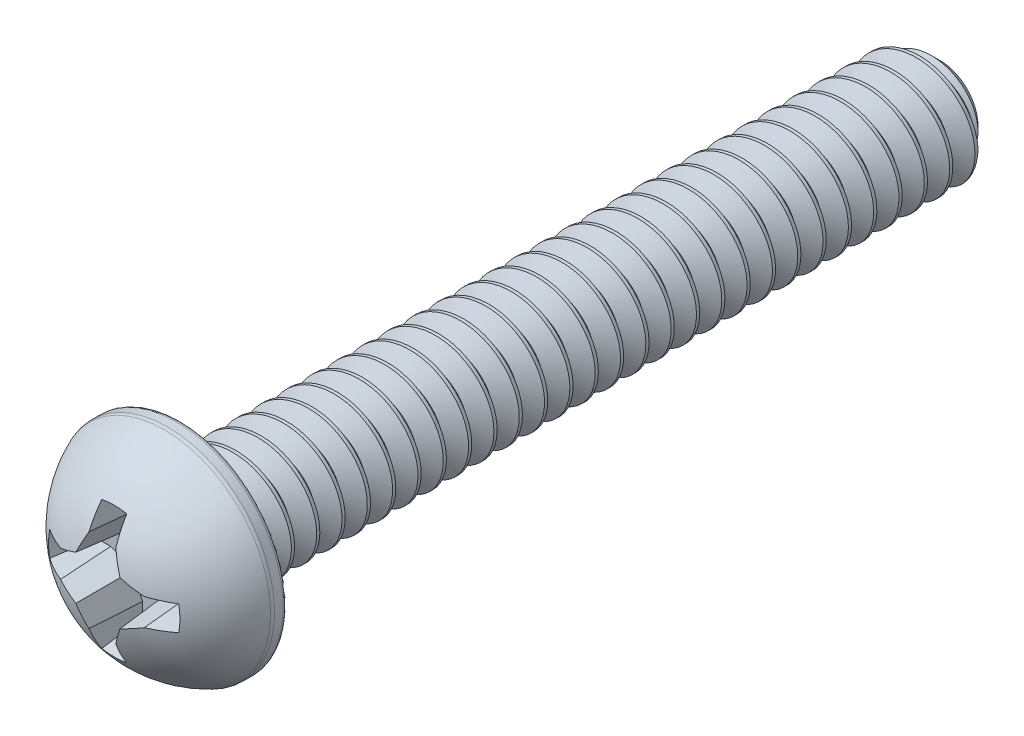
SolidWorks part; units mm, degrees
ref_plane "Front" through (0, 0, 0) normal (0, 0, 1) x (1, 0, 0)
ref_plane "Top" through (0, 0, 0) normal (0, 1, 0) x (1, 0, 0)
ref_plane "Right" through (0, 0, 0) normal (1, 0, 0) x (0, 0, -1)
sketch "Sketch1" plane through (0, 0, 0) normal (0, 0, 1) x (1, 0, 0)
  circle A0 centre (0, 0) radius 2.6797
  dimension "Head Dia" = 5.3594
extrude "Extrude3" add sketch "Sketch1" along normal blind 2.1844
sketch "Sketch11" plane through (0, 0, 0) normal (1, 0, 0) x (0, 0, -1)
  line L0 (0, 0) -> (-2.4384, 0) construction
  line L4 (-2.1844, 2.6797) -> (-2.1844, -2.6797) construction
  line L5 (-2.4384, 3.1064) -> (0, 3.1064)
  line L7 (0, 3.1064) -> (0, 2.5705)
  line L8 (-0.3277, 2.6797) -> (-0.1092, 2.6797)
  line L9 (0, -2.6797) -> (0, 2.6797) construction
  line L11 (0, 2.6797) -> (-2.1844, 2.6797) construction
  line L13 (-2.1844, 0) -> (-2.4384, 0)
  line L14 (-2.4384, 0) -> (-2.4384, 3.1064)
  arc A0 (-0.412, 2.6628) -> (-2.1844, 0) centre (0.702, 0) ccw
  arc A1 (-0.1092, 2.6797) -> (0, 2.5705) centre (-0.1092, 2.5705) cw
  arc A2 (-0.412, 2.6628) -> (-0.3277, 2.6797) centre (-0.3277, 2.4613) cw
  dimension "D2" = 0.1092
  dimension "D4" = 0.2184
  dimension "D3" = 0.254
  dimension "D1" = 0.2184
  dimension "D5" = 0.5359
revolve "Cut-Revolve3" cut sketch "Sketch11" angle 360 about L0
sketch "Sketch4" plane through (0, 0, 0) normal (1, 0, 0) x (0, 0, -1)
  line L0 (0, 0) -> (19.05, 0)
  line L3 (19.05, 0) -> (19.05, 1.4224)
  line L4 (19.05, 1.4224) -> (0, 1.4224)
  line L6 (0, 1.4224) -> (0, 0)
  line L9 (19.05, 1.4224) -> (19.05, -1.4224) construction
  dimension "length" = 19.05
  dimension "dia" = 2.8448
revolve "Revolve1" add sketch "Sketch4" angle 360 about L0
chamfer "Chamfer1" distance 0.4763 angle 45 1 edges at (1.4224, 0, -19.05)
sketch "Sketch13" plane through (0, 0, -19.05) normal (0, 0, -1) x (-1, 0, 0)
  circle A2 centre (0, 0) radius 1.4224
curve "Helix/Spiral1" pitch 0.635 height 20.955 turns 33
sketch "Sketch14" plane through (0, 0, 0) normal (1, 0, 0) x (0, 0, -1)
  line L0 (19.05, 1.4224) -> (19.6056, 1.4224)
  line L1 (19.6056, 1.4224) -> (19.3675, 0.9928)
  line L2 (19.3675, 0.9928) -> (19.2881, 0.9928)
  line L3 (19.2881, 0.9928) -> (19.05, 1.4224)
  line L4 (19.1691, 1.2076) -> (19.4866, 1.2076) construction
  dimension "D1" = 0.0794
  dimension "D2" = 58
  dimension "D3" = 0.3175
sweep "Cut-Sweep1" cut profiles "Sketch14" path "Helix/Spiral1"
ref_plane "Plane1" through (0, 0, 19.05) normal (0, 0, -1) x (-1, 0, 0)
sketch "Sketch29" [suppressed] plane through (0, 0, -38.1) normal (0, 0, -1) x (-1, 0, 0)
  circle A0 centre (0, 0) radius 4.7625 construction
  circle A1 centre (0, 0) radius 4.7625
  point P3 (0, -4.7625)
extrude "Extrude11" [suppressed] add sketch "Sketch29" against normal up to surface (38.1 mm away)
sketch "Sketch26" plane through (0, 0, 0) normal (0, 0, 1) x (1, 0, 0)
  circle A1 centre (0, 0) radius 0.5461
  dimension "D1" = 1.0922
extrude "Extrude8" add sketch "Sketch26" along normal up to surface (2.1323 mm away)
ref_plane "Plane2" through (0, 0, 2.1844) normal (0, 0, 1) x (1, 0, 0)
sketch "Sketch12" plane through (0, 0, 2.1844) normal (0, 0, 1) x (1, 0, 0)
  line L0 (0, 0) -> (0.3573, 0.3573) construction
  line L1 (0, 0) -> (0, -1.1128) construction
  line L2 (1.7504, 0.3573) -> (1.0538, 0.3573)
  line L3 (0, 1.7865) -> (0, 2.6797) construction
  line L8 (0.3573, 1.0538) -> (0.3573, 1.7504)
  line L9 (0.3573, 0.3573) -> (1.0538, 1.0538) construction
  line L10 (1.0538, 0.3573) -> (0.5613, 0.5613)
  line L11 (0.5613, 0.5613) -> (0.3573, 1.0538)
  line L12 (1.0538, 0.3573) -> (0.3573, 0.3573) construction
  line L13 (0.3573, 1.0538) -> (0.3573, 0.3573) construction
  line L14 (0, 0) -> (0, 1.7865)
  line L15 (0, 0) -> (1.7865, 0)
  circle A1 centre (0, 0) radius 2.6797 construction
  arc A2 (1.7865, 0) -> (1.7504, 0.3573) centre (0, 0) ccw
  arc A3 (0.3573, 1.7504) -> (0, 1.7865) centre (0, 0) ccw
  circle A5 centre (0, 0) radius 1.1128 construction
  arc A6 (1.0538, 0.3573) -> (0.3573, 1.0538) centre (1.0538, 1.0538) cw construction
  dimension "Phillips Dia" = 3.5729
  dimension "Phillips Width" = 0.7146
  dimension "D1" = 0.8932
extrude "Cut-Extrude3" cut sketch "Sketch12" against normal blind 1.4563
pattern_circular "CirPattern1" count 4 over 360 about axis through (0, 0, 0) along (0, 0, 1) of "Cut-Extrude3"
draft "Draft1" type of draft neutral plane draft angle 15 neutral plane "Plane2" faces to draft 4 face at (-1.7684, 0, 1.1466) face at (0, -1.7684, 1.1466) face at (1.7684, 0, 1.1466) face at (0, 1.7684, 1.1466) neutral plane through (0, 0, 2.1844) neutral plane normal (0, 0, 1) parameters "D1"=15
draft "Draft2" type of draft neutral plane draft angle 5 neutral plane "Plane2" faces to draft 16 face at (0.3573, 1.2362, 1.1577) face at (0.459, 0.8082, 1.3759) face at (0.8082, 0.459, 1.3759) face at (1.2362, 0.3573, 1.1577) face at (1.2362, -0.3573, 1.1577) face at (0.8082, -0.459, 1.3759) face at (0.459, -0.8082, 1.3759) face at (0.3573, -1.2362, 1.1577) face at (-0.3573, -1.2362, 1.1577) face at (-0.459, -0.8082, 1.3759) face at (-0.8082, -0.459, 1.3759) face at (-1.2362, -0.3573, 1.1577) face at (-1.2362, 0.3573, 1.1577) face at (-0.8082, 0.459, 1.3759) face at (-0.459, 0.8082, 1.3759) face at (-0.3573, 1.2362, 1.1577) neutral plane through (0, 0, 2.1844) neutral plane normal (0, 0, 1) parameters "D1"=5
sketch "Sketch18" plane through (0, 0, 0) normal (1, 0, 0) x (0, 0, -1)
  line L1 (19.05, 1.4224) -> (0, 1.4224) construction
  point P0 (18.0975, -1.4224)
  point P1 (18.415, 1.4224)
  point P2 (-2.1844, 0.5613)
  dimension "D1" = 0.635
  dimension "D2" = 0.9525
equation "\"Phillips Dia@Sketch12\"=\"Head Dia@Sketch1\"/1.5"
equation "\"Phillips Width@Sketch12\"=\"Phillips Dia@Sketch12\"/5"
equation "\"Phillips Depth@Cut-Extrude3\"= \"Head Ht@Extrude3\" / 1.5"
equation "\"D3@Helix/Spiral1\" = \"length@Sketch4\" + \"D4@Helix/Spiral1\" + .05"
equation "\"D1@Sketch14\" = \"D4@Helix/Spiral1\" * .125"
equation "\"D3@Sketch14\" = \"D4@Helix/Spiral1\" * .5"
equation "\"D1@Sketch11\" = \"Head Ht@Extrude3\" / 10"
equation "\"D2@Sketch11\" = \"D1@Sketch11\" / 2"
equation "\"D4@Sketch11\" = \"D1@Sketch11\""
equation "\"D5@Sketch11\" = \"Head Dia@Sketch1\" / 10"
equation "\"D1@Chamfer1\" = \"D4@Helix/Spiral1\" * .75"
equation "\"D1@Sketch18\" = \"D4@Helix/Spiral1\""
equation "\"D2@Sketch18\" = \"D4@Helix/Spiral1\" * 1.5"
